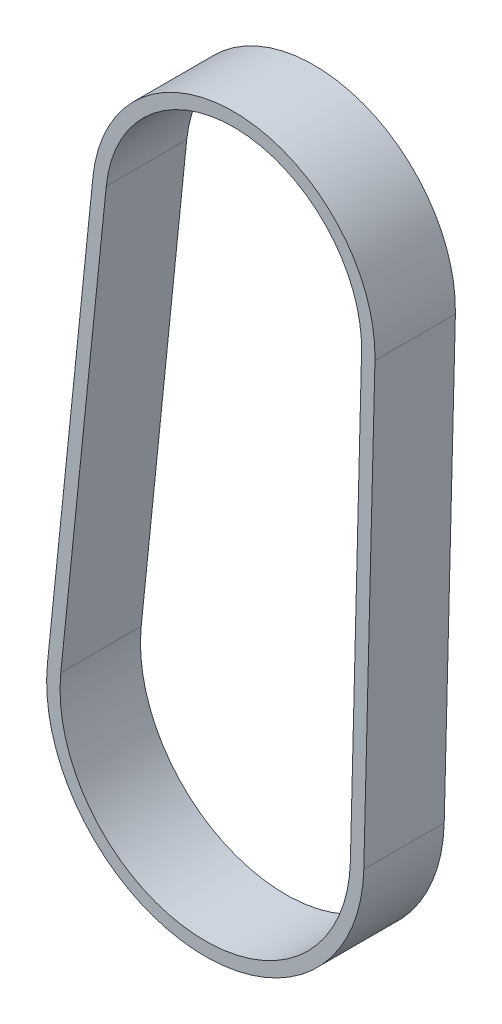
SolidWorks part; units mm, degrees
ref_plane "Front Plane" through (0, 0, 0) normal (0, 0, 1) x (1, 0, 0)
ref_plane "Top Plane" through (0, 0, 0) normal (0, 1, 0) x (1, 0, 0)
ref_plane "Right Plane" through (0, 0, 0) normal (1, 0, 0) x (0, 0, -1)
sketch "Sketch2" plane through (0, 0, 0) normal (0, 0, 1) x (1, 0, 0)
  line L0 (0, 0) -> (1, 0) construction
  line L1 (0, 0) -> (0, 1) construction
  line L4 (-19.3404, -48.2433) -> (-14.2494, 1.4596)
  line L5 (14.3195, -0.3582) -> (13.0699, -50.3055)
  arc A2 (13.0699, -50.3055) -> (-19.3404, -48.2433) centre (-3.175, -49.8991) cw
  arc A3 (-14.2494, 1.4596) -> (14.3195, -0.3582) centre (0, 0) cw
extrude "Extrude-Thin1" add sketch "Sketch2" against normal blind 9 thin thin type one direction wall 1.5
